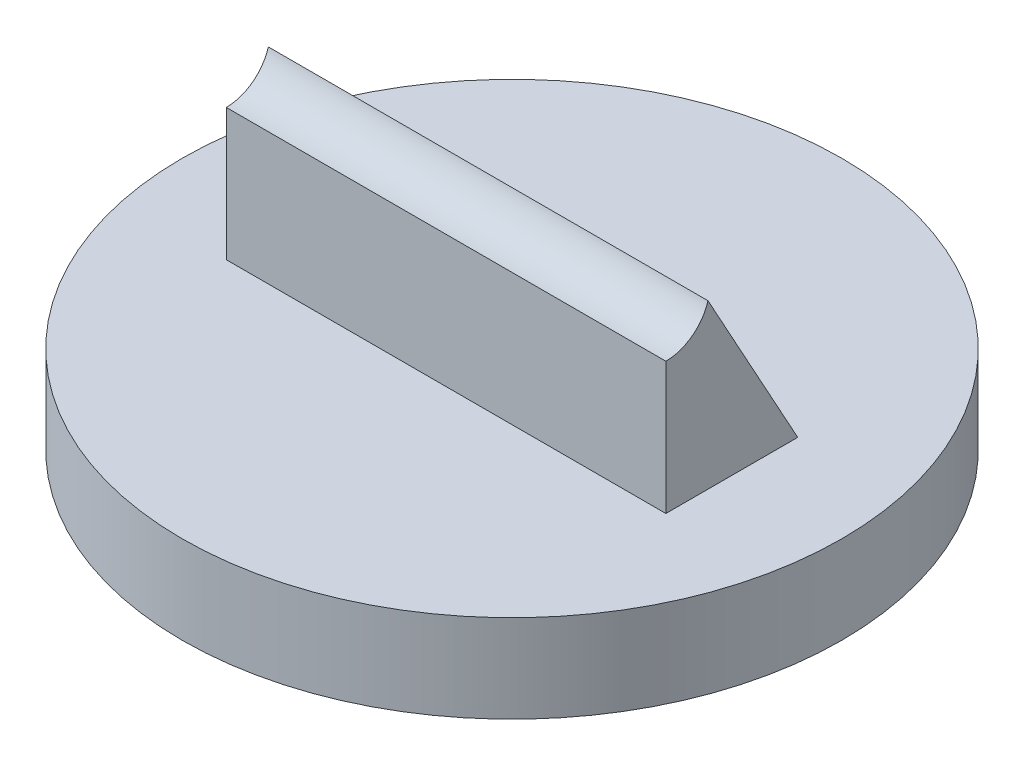
SolidWorks part; units mm, degrees
ref_plane "Ebene vorne" through (0, 0, 0) normal (0, 0, 1) x (1, 0, 0)
ref_plane "Ebene oben" through (0, 0, 0) normal (0, 1, 0) x (1, 0, 0)
ref_plane "Ebene rechts" through (0, 0, 0) normal (1, 0, 0) x (0, 0, -1)
sketch "Skizze1" plane through (0, 0, 0) normal (0, 1, 0) x (1, 0, 0)
  circle A0 centre (0, 0) radius 75
  dimension "D1" = 150
extrude "Aufsatz-Linear austragen1" add sketch "Skizze1" along normal blind 20
sketch "Skizze2" plane through (0, 20, 0) normal (0, 1, 0) x (1, 0, 0)
  line L1 (-50, 15) -> (50, 15)
  line L2 (-50, 15) -> (-50, -15)
  line L3 (-50, -15) -> (50, -15)
  line L4 (50, 15) -> (50, -15)
  line L5 (-50, 15) -> (50, -15) construction
  line L6 (-50, -15) -> (50, 15) construction
  point P0 (0, 0)
  dimension "D1" = 30
  dimension "D2" = 100
extrude "Aufsatz-Linear austragen2" add sketch "Skizze2" along normal blind 40
sketch "Skizze3" plane through (50, 0, 0) normal (1, 0, 0) x (0, 0, -1)
  circle A0 centre (-15, 60) radius 10
  dimension "D1" = 20
extrude "Schnitt-Linear austragen2" cut sketch "Skizze3" against normal blind 100 contours A0
sketch "Skizze4" plane through (50, 0, 0) normal (1, 0, 0) x (0, 0, -1)
  line L1 (15, 20) -> (15, 60)
  line L3 (15, 60) -> (-7, 60)
  line L4 (-7, 60) -> (15, 20)
  dimension "D1" = 22
extrude "Schnitt-Linear austragen3" cut sketch "Skizze4" against normal blind 100
